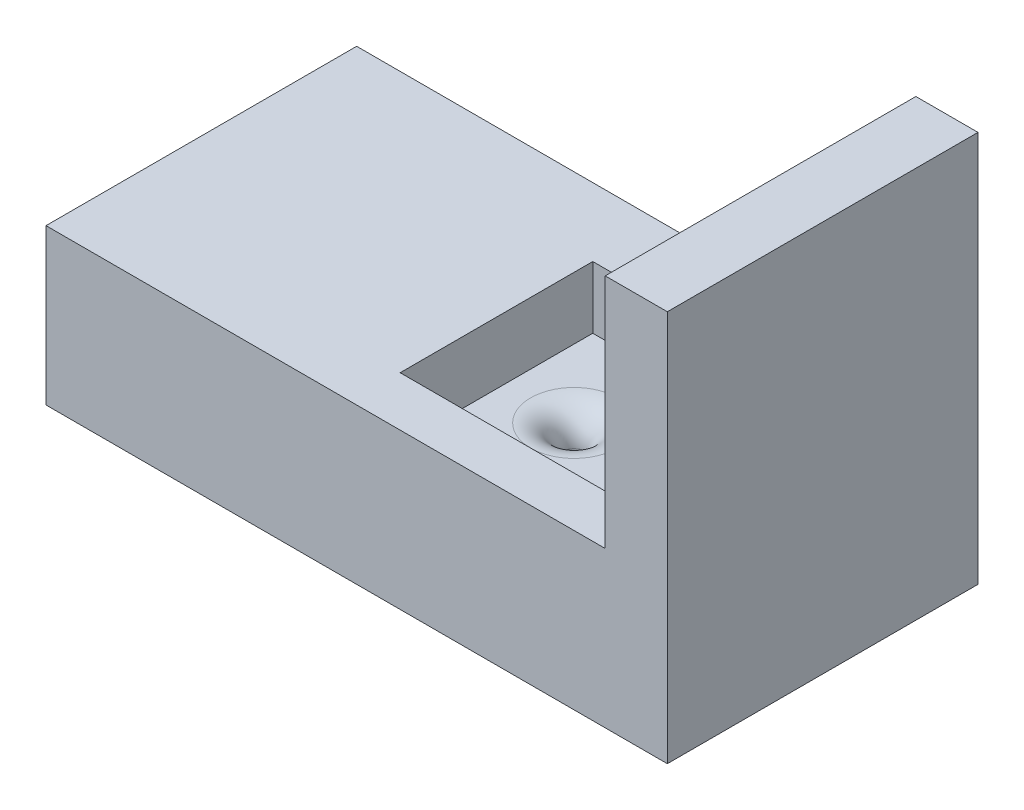
SolidWorks part; units mm, degrees
ref_plane "Front Plane" through (0, 0, 0) normal (0, 0, 1) x (1, 0, 0)
ref_plane "Top Plane" through (0, 0, 0) normal (0, 1, 0) x (1, 0, 0)
ref_plane "Right Plane" through (0, 0, 0) normal (1, 0, 0) x (0, 0, -1)
sketch "Sketch1" plane through (0, 0, 0) normal (0, 1, 0) x (1, 0, 0)
  line L1 (70, 25) -> (-30, 25)
  line L2 (-30, 25) -> (-30, -25)
  line L3 (-30, -25) -> (70, -25)
  line L4 (60, 14) -> (60, -17)
  line L5 (60, 14) -> (19, 14)
  line L6 (60, -17) -> (19, -17)
  line L7 (19, 14) -> (19, -17)
  line L13 (70, 25) -> (70, -25)
  dimension "D1" = 8
  dimension "D2" = 10
  dimension "D3" = 100
  dimension "D5" = 41
  dimension "D7" = 50
extrude "Boss-Extrude1" add sketch "Sketch1" along normal blind 10
sketch "Sketch2" plane through (0, 0, 25) normal (0, 0, 1) x (1, 0, 0)
  line L1 (70, 10) -> (60, 10)
  line L2 (70, 10) -> (70, 48)
  line L3 (70, 48) -> (60, 48)
  line L4 (60, 10) -> (60, 48)
  dimension "D1" = 10
  dimension "D2" = 38
extrude "Boss-Extrude2" add sketch "Sketch2" against normal blind 50
sketch "Sketch10" plane through (0, 0, 0) normal (0, -1, 0) x (1, 0, 0)
  line L0 (55, 0) -> (-55, 0) construction
  line L1 (-30, 25) -> (70, 25)
  line L2 (-30, 25) -> (-30, -25)
  line L3 (-30, -25) -> (70, -25)
  line L4 (70, 25) -> (70, -25)
  circle A0 centre (30, 0) radius 2
  dimension "D1" = 4
  dimension "D2" = 40
extrude "Boss-Extrude6" add sketch "Sketch10" along normal blind 5
sketch "Sketch12" plane through (0, 0, 0) normal (0, 0, 1) x (1, 0, 0)
  line L0 (70, -5) -> (-30, -5) construction
  line L1 (32, -5) -> (33.8, -5)
  line L2 (32, -5) -> (32, -15)
  line L3 (32, -15) -> (33.8, -15)
  line L4 (33.8, -5) -> (33.8, -15)
  line L5 (30, -5) -> (30, -10.9855) construction
  line L6 (70, 48) -> (70, -5) construction
  dimension "D1" = 40
  dimension "D2" = 3.8
  dimension "D3" = 2
  dimension "D4" = 10
revolve "Revolve3" add sketch "Sketch12" angle 360 about L5
fillet "Fillet4" radius 2 1 edges at (30, -5, 3.8)
sketch "Sketch13" plane through (0, -5, 0) normal (0, -1, 0) x (1, 0, 0)
  line L1 (-30, 25) -> (70, 25)
  line L2 (-30, 25) -> (-30, -25)
  line L3 (-30, -25) -> (70, -25)
  line L4 (70, 25) -> (70, -25)
  circle A0 centre (30, 0) radius 6
  dimension "D1" = 12
extrude "Boss-Extrude7" add sketch "Sketch13" along normal blind 10
fillet "Fillet5" radius 5 1 edges at (30, 0, -2)
